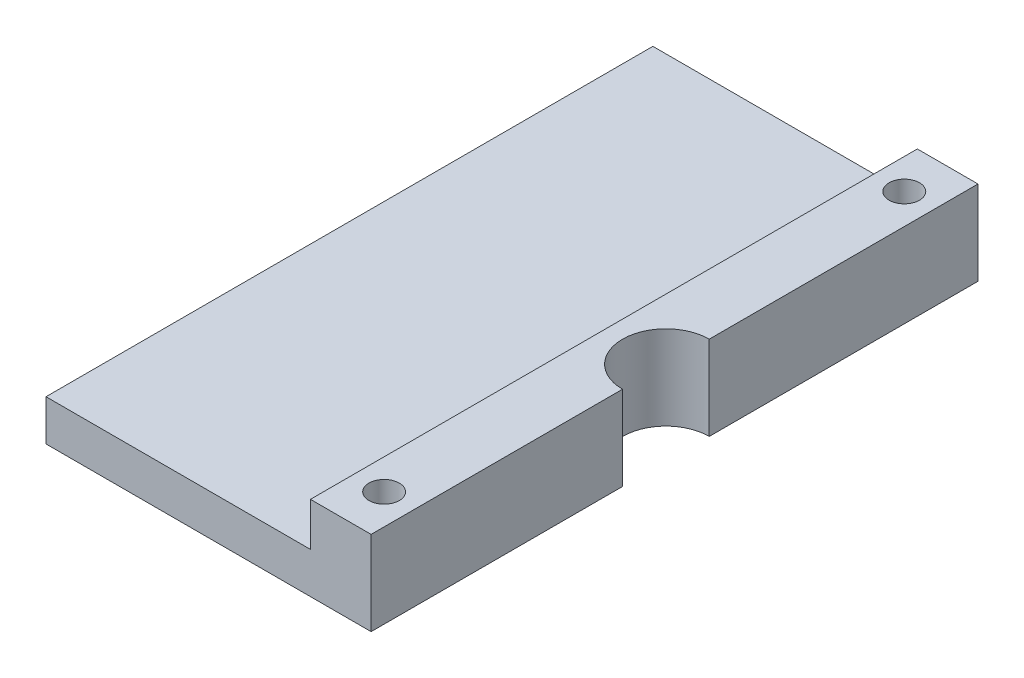
SolidWorks part; units mm, degrees
ref_plane "Front Plane" through (0, 0, 0) normal (0, 0, 1) x (1, 0, 0)
ref_plane "Top Plane" through (0, 0, 0) normal (0, 1, 0) x (1, 0, 0)
ref_plane "Right Plane" through (0, 0, 0) normal (1, 0, 0) x (0, 0, -1)
sketch "Sketch1" plane through (0, 0, 0) normal (0, 1, 0) x (1, 0, 0)
  line L1 (0, 0) -> (41.275, 0)
  line L2 (0, 0) -> (0, 88.9)
  line L3 (0, 88.9) -> (41.275, 88.9)
  line L4 (41.275, 0) -> (41.275, 88.9)
  line L5 (41.275, 88.9) -> (50.165, 88.9)
  line L6 (41.275, 88.9) -> (41.275, 0)
  line L7 (41.275, 0) -> (50.165, 0)
  line L8 (50.165, 88.9) -> (50.165, 0)
  dimension "D1" = 41.275
  dimension "D2" = 88.9
  dimension "D3" = 8.89
extrude "Boss-Extrude1" add sketch "Sketch1" along normal blind 5.9944 contours L1 L4 L3 L2 region at (20.6375, 0, -44.45)
extrude "Boss-Extrude2" add sketch "Sketch1<5>" along normal blind 12.3444 contours L8 L5 L4 L7 region at (45.72, 0, -44.45)
sketch "Sketch1<5>" plane through (0, 0, 0) normal (0, 1, 0) x (1, 0, 0) same geometry as "Sketch1"
sketch "Sketch3" plane through (0, 12.3444, 0) normal (0, 1, 0) x (1, 0, 0)
  line L0 (45.72, 82.55) -> (45.72, 6.35) construction
  line L1 (50.165, 88.9) -> (50.165, 0) construction
  line L2 (41.275, 88.9) -> (50.165, 88.9) construction
  line L3 (0, 0) -> (0, 88.9) construction
  circle A0 centre (45.72, 82.55) radius 2.2225
  circle A1 centre (45.72, 6.35) radius 2.2225
  point P4 (45.72, 44.45)
  point P6 (50.165, 44.45)
  point P7 (45.72, 88.9)
  dimension "D1" = 4.445
  dimension "D2" = 4.445
  dimension "D3" = 76.2
  dimension "D4" = 45.72
extrude "Cut-Extrude1" cut sketch "Sketch3" against normal through all both contours A1 | A0
sketch "Sketch4" plane through (0, 0, 0) normal (0, -1, 0) x (1, 0, 0)
  circle A0 centre (45.72, -6.35) radius 3.683
  circle A1 centre (45.72, -82.55) radius 3.683
  dimension "D1" = 7.366
  dimension "D2" = 7.366
extrude "Cut-Extrude2" cut sketch "Sketch4" against normal blind 4.064
sketch "Sketch5" plane through (0, 5.9944, 0) normal (0, 1, 0) x (1, 0, 0)
  line L0 (0, 0) -> (41.275, 0) construction
  line L1 (0, 88.9) -> (2.54, 88.9)
  line L2 (0, 88.9) -> (0, 0)
  line L3 (0, 0) -> (2.54, 0)
  line L4 (2.54, 88.9) -> (2.54, 0)
  dimension "D1" = 2.54
extrude "Cut-Extrude3" cut sketch "Sketch5" against normal through all both
sketch "Sketch6" plane through (0, 12.3444, 0) normal (0, 1, 0) x (1, 0, 0)
  line L1 (41.275, 0) -> (50.165, 0) construction
  line L2 (50.165, 88.9) -> (50.165, 0) construction
  circle A0 centre (50.165, 43.18) radius 6.35
  dimension "D1" = 12.7
  dimension "D2" = 43.18
extrude "Cut-Extrude4" cut sketch "Sketch6" against normal through all both and the other way through all
